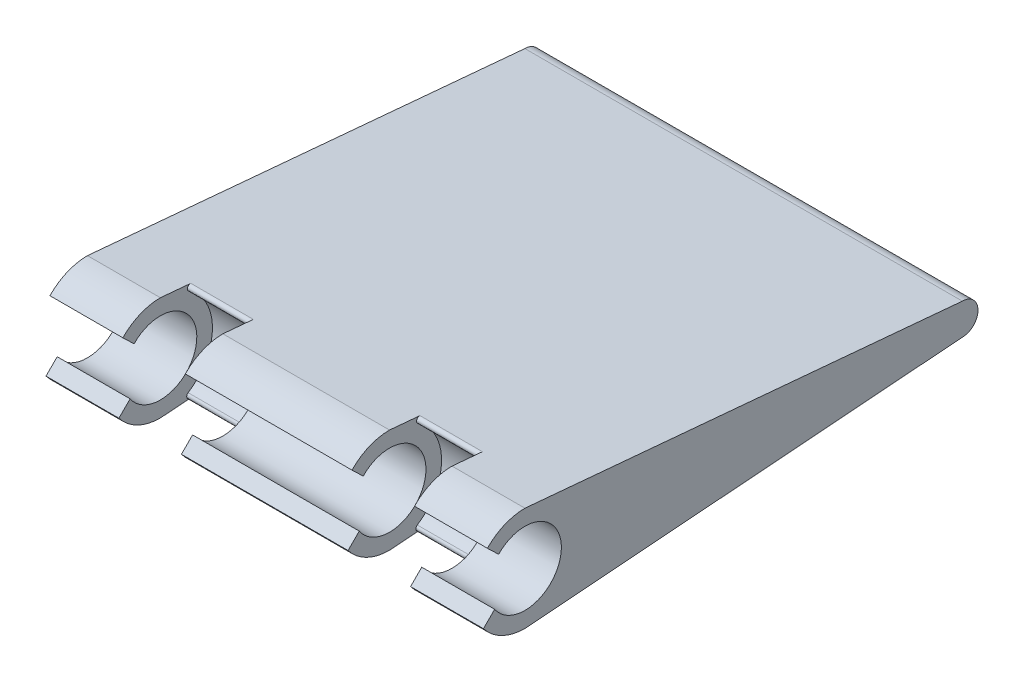
SolidWorks part; units mm, degrees
ref_plane "Front Plane" through (0, 0, 0) normal (0, 0, 1) x (1, 0, 0)
ref_plane "Top Plane" through (0, 0, 0) normal (0, 1, 0) x (1, 0, 0)
ref_plane "Right Plane" through (0, 0, 0) normal (1, 0, 0) x (0, 0, -1)
sketch "Sketch1" plane through (0, 0, 0) normal (1, 0, 0) x (0, 0, -1)
  line L0 (42, 1.2185) -> (0, 5)
  line L1 (0, -5) -> (42, -1.7815)
  circle A0 centre (0, 0) radius 5
  circle A1 centre (0, 0) radius 3.5
  circle A2 centre (42, -0.2815) radius 1.5
  dimension "D1" = 10
  dimension "D2" = 7
  dimension "D3" = 3
  dimension "D4" = 42
extrude "Boss-Extrude1" add sketch "Sketch1" along normal mid plane 42 contours A2 L0 A0 L1 | L0 A0 L1 A1 | A2 region at (0, -0.1325, -19.4361) region at (0, -0.2815, -42) region at (0, 3.1136, -3.7298)
extrude "Cut-Extrude1" cut sketch "Sketch1<3>" along normal blind 6 from offset 8 contours L0 A0 L1 A1 | A0 | A1 region at (0, 3.1136, -3.7298)
sketch "Sketch1<3>" plane through (0, 0, 0) normal (1, 0, 0) x (0, 0, -1) same geometry as "Sketch1"
extrude "Cut-Extrude2" cut sketch "Sketch1<4>" against normal blind 6 from offset 8 contours L0 A0 L1 A1 | A0 | A1 region at (0, 3.1136, -3.7298) offset against normal yes
sketch "Sketch1<4>" plane through (0, 0, 0) normal (1, 0, 0) x (0, 0, -1) same geometry as "Sketch1"
fillet "Fillet2" radius 0.3 4 edges at (11, -4.9416, -0.7618) (-11, -4.9416, -0.7618) (11, 4.9196, -0.8931) (-11, 4.9196, -0.8931)
sketch "Sketch2" plane through (21, 0, 0) normal (1, 0, 0) x (0, 0, -1)
  line L0 (-3.6021, 3.4677) -> (-2.5215, 2.4274)
  line L1 (-3.9799, -3.0267) -> (-2.9051, -1.952)
  circle A0 centre (0, 0) radius 3.5 construction
  arc A1 (0, 5) -> (0, -5) centre (0, 0) ccw construction
  arc A2 (-2.5215, 2.4274) -> (-2.9051, -1.952) centre (0, 0) ccw
  arc A3 (-3.6021, 3.4677) -> (-3.9799, -3.0267) centre (0, 0) ccw
extrude "Cut-Extrude3" cut sketch "Sketch2" against normal up to surface (42 mm away) up to face at (-21, -0.1407, -20.125)
